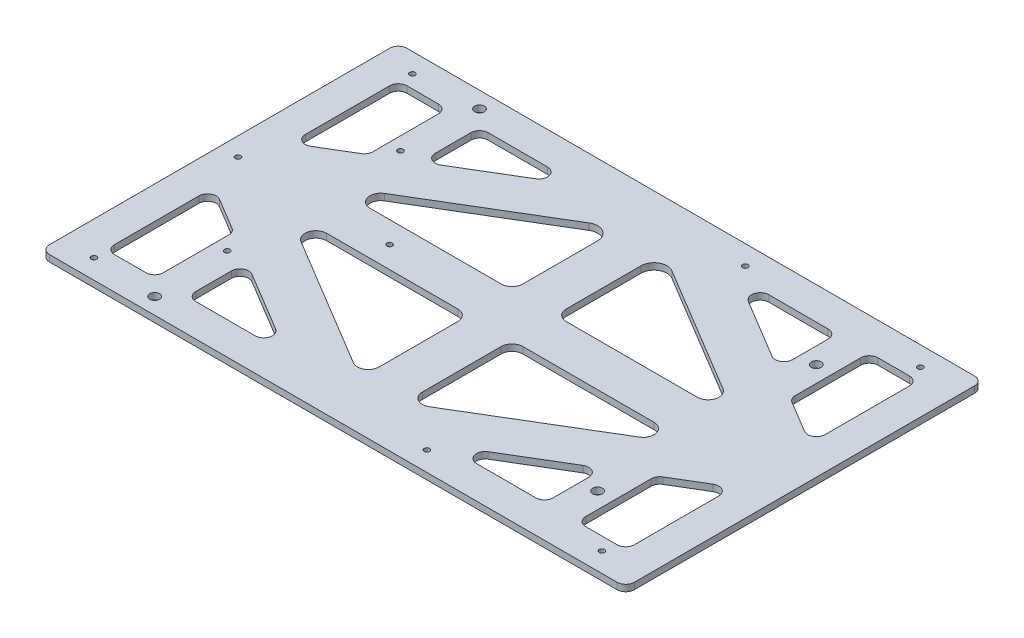
SolidWorks part; units mm, degrees
ref_plane "Alzado" through (0, 0, 0) normal (0, 0, 1) x (1, 0, 0)
ref_plane "Planta" through (0, 0, 0) normal (0, 1, 0) x (1, 0, 0)
ref_plane "Vista lateral" through (0, 0, 0) normal (1, 0, 0) x (0, 0, -1)
sketch "Croquis1" plane through (0, 0, 0) normal (0, 1, 0) x (1, 0, 0)
  line L1 (135, -82.5) -> (-135, -82.5)
  line L2 (135, -82.5) -> (135, 82.5)
  line L3 (135, 82.5) -> (-135, 82.5)
  line L4 (-135, -82.5) -> (-135, 82.5)
  line L5 (135, -82.5) -> (-135, 82.5) construction
  line L6 (135, 82.5) -> (-135, -82.5) construction
  point P0 (0, 0)
  dimension "D1" = 165
  dimension "D2" = 270
extrude "Saliente-Extruir1" add sketch "Croquis1" along normal blind 3
fillet "Redondeo1" radius 4 4 edges at (-135, 1.5, -82.5) (135, 1.5, -82.5) (135, 1.5, 82.5) (-135, 1.5, 82.5)
sketch "Croquis2" plane through (0, 3, 0) normal (0, 1, 0) x (1, 0, 0)
  line L0 (131, 82.5) -> (-131, 82.5) construction
  line L1 (135, -78.5) -> (135, 78.5) construction
  circle A0 centre (90, 50.5) radius 2.25
  dimension "D1" = 4.5
  dimension "D2" = 32
  dimension "D3" = 45
extrude "Cortar-Extruir1" cut sketch "Croquis2" against normal through all
mirror "Simetría1" about plane through (0, 0, 0) normal (0, 0, 1) of "Cortar-Extruir1"
sketch "Croquis3" plane through (0, 3, 0) normal (0, 1, 0) x (1, 0, 0)
  line L0 (-135, 78.5) -> (-135, -78.5) construction
  line L1 (131, 82.5) -> (-131, 82.5) construction
  line L2 (-135, 0) -> (-113.8944, 0) construction
  circle A0 centre (-90, 75) radius 2.25
  circle A1 centre (-90, -75) radius 2.25
  dimension "D1" = 4.5
  dimension "D2" = 45
  dimension "D3" = 7.5
extrude "Cortar-Extruir2" cut sketch "Croquis3" against normal through all
sketch "Croquis4" plane through (0, 3, 0) normal (0, 1, 0) x (1, 0, 0)
  line L0 (0, 82.5) -> (0, -82.5) construction
  line L1 (131, 82.5) -> (-131, 82.5) construction
  line L2 (-131, -82.5) -> (131, -82.5) construction
  line L3 (-135, 0) -> (135, 0) construction
  line L4 (-135, 78.5) -> (-135, -78.5) construction
  line L5 (135, -78.5) -> (135, 78.5) construction
  line L6 (0, -82.5) -> (131, -82.5) construction
  line L7 (135, -82.5) -> (135, 78.5) construction
  line L8 (131, 82.5) -> (0, 82.5) construction
  line L9 (116, 67.5) -> (101.5, 67.5)
  line L12 (110.2817, 0) -> (2.6409, -64.5845) construction
  line L13 (131, 67.5) -> (-131, 67.5) construction
  line L14 (4.9275, 63.2125) -> (110.2817, 0) construction
  line L15 (15, 10) -> (75.5635, 10)
  line L16 (131, 82.5) -> (-131, 82.5) construction
  line L17 (15, -10) -> (75.5635, -10)
  line L18 (10, 49.5719) -> (10, 15)
  line L19 (19.087, 54.7169) -> (78.136, 19.2875)
  line L20 (78.136, -19.2875) -> (17.5725, -55.6256)
  line L24 (49.038, 60.07) -> (76.442, 43.6276)
  line L29 (15.2174, 80.3624) -> (149.1548, 0) construction
  line L30 (90, 50.5) -> (90, 67.5) construction
  line L31 (149.1548, 0) -> (12.9308, -81.7344) construction
  line L32 (99.442, 29.8276) -> (113.942, 21.1276)
  line L34 (82.5, 63.5) -> (82.5, 47.0576)
  line L36 (97.5, 63.5) -> (97.5, 33.2576)
  line L37 (120, 24.5576) -> (120, 63.5)
  line L38 (78.5, 67.5) -> (51.096, 67.5)
  line L39 (10, -15) -> (10, -51.3381)
  arc A0 (78.5, 67.5) -> (82.5, 63.5) centre (78.5, 63.5) cw
  arc A1 (82.5, 47.0576) -> (76.442, 43.6276) centre (78.5, 47.0576) cw
  arc A2 (49.038, 60.07) -> (51.096, 67.5) centre (51.096, 63.5) cw
  arc A3 (120, 63.5) -> (116, 67.5) centre (116, 63.5) ccw
  arc A4 (120, 24.5576) -> (113.942, 21.1276) centre (116, 24.5576) cw
  arc A5 (99.442, 29.8276) -> (97.5, 33.2576) centre (101.5, 33.2576) cw
  arc A6 (101.5, 67.5) -> (97.5, 63.5) centre (101.5, 63.5) ccw
  arc A7 (10, -51.3381) -> (17.5725, -55.6256) centre (15, -51.3381) ccw
  arc A9 (10, 49.5719) -> (19.087, 54.7169) centre (16, 49.5719) cw
  arc A10 (75.5635, 10) -> (78.136, 19.2875) centre (75.5635, 15) ccw
  arc A11 (75.5635, -10) -> (78.136, -19.2875) centre (75.5635, -15) cw
  arc A12 (15, 10) -> (10, 15) centre (15, 15) cw
  arc A13 (15, -10) -> (10, -15) centre (15, -15) ccw
  point P44 (97.5, 30.9929)
  point P64 (10, -10)
  dimension "D5" = 4
  dimension "D6" = 4
  dimension "D7" = 5
  dimension "D13" = 5
  dimension "D14" = 5
  dimension "D2" = 22.43
  dimension "D4" = 15
  dimension "D8" = 15
  dimension "D9" = 38.8724
  dimension "D10" = 10
  dimension "D11" = 10
  dimension "D12" = 10
  dimension "D1" = 15
  dimension "D3" = 20
extrude "Cortar-Extruir3" cut sketch "Croquis4" against normal through all
mirror "Simetría2" about plane through (0, 0, 0) normal (0, 0, 1) of face at (117.4709, 1.5, -21.9597) of face at (106.692, 1.5, -25.4776) of face at (98.2451, 1.5, -31.4147) of face at (97.5, 1.5, -48.3788) of face at (99.0858, 1.5, -65.9142) of face at (108.75, 1.5, -67.5) of face at (118.4142, 1.5, -65.9142) of face at (120, 1.5, -44.0288) of face at (80.9142, 1.5, -65.9142) of face at (82.5, 1.5, -55.2788) of face at (79.9709, 1.5, -44.4597) of face at (62.74, 1.5, -51.8488) of face at (48.6541, 1.5, -64.1764) of face at (64.798, 1.5, -67.5)
mirror "Simetría4" about plane through (0, 0, 0) normal (1, 0, 0) of "Cortar-Extruir3"
mirror "Simetría6" about plane through (0, 0, 0) normal (0, 0, 1) of face at (-64.798, 1.5, -67.5) of face at (-48.6541, 1.5, -64.1764) of face at (-62.74, 1.5, -51.8488) of face at (-79.9709, 1.5, -44.4597) of face at (-80.9142, 1.5, -65.9142) of face at (-82.5, 1.5, -55.2788) of face at (-97.5, 1.5, -48.3788) of face at (-98.2451, 1.5, -31.4147) of face at (-106.692, 1.5, -25.4776) of face at (-117.4709, 1.5, -21.9597) of face at (-120, 1.5, -44.0288) of face at (-99.0858, 1.5, -65.9142) of face at (-118.4142, 1.5, -65.9142) of face at (-108.75, 1.5, -67.5)
sketch "Croquis5" plane through (0, 3, 0) normal (0, 1, 0) x (1, 0, 0)
  line L0 (135, -78.5) -> (135, 78.5) construction
  line L1 (-131, -82.5) -> (131, -82.5) construction
  line L2 (131, 82.5) -> (-131, 82.5) construction
  circle A0 centre (-119.5, 73.5) radius 1.75
  circle A1 centre (34.2, 73.5) radius 1.75
  circle A2 centre (115, 73.5) radius 1.75
  circle A3 centre (115, -73.5) radius 1.75
  circle A4 centre (34.2, -73.5) radius 1.75
  circle A5 centre (-119.5, -73.5) radius 1.75
  point P0 (-119.5, 73.5)
  point P3 (34.2, 73.5)
  point P6 (115, 73.5)
  point P9 (115, -73.5)
  point P12 (34.2, -73.5)
  point P15 (-119.5, -73.5)
  dimension "D1" = 20
  dimension "D2" = 80.8
  dimension "D3" = 153.7
  dimension "D4" = 9
  dimension "D5" = 9
hole_wizard "Taladro roscado M31" positions "Croquis5" profile "Croquis6" tap size "M3" standard "ISO"
sketch "Croquis6" plane through (-119.5, 3, -73.5) normal (1, 0, 0) x (0, 0, 1)
  line L0 (0, 0) -> (0, 9.2511)
  line L1 (0, 9.2511) -> (1.25, 8.5)
  line L2 (1.25, 8.5) -> (1.25, 0)
  line L5 (1.25, 0) -> (0, 0)
  line L10 (0, 9.2511) -> (-1.25, 8.5) construction
  line L11 (0, -6.35) -> (0, 107.95) construction
  dimension "Diámetro de perforador para roscar" = 2.5
  dimension "Profundidad de perforador para roscar" = 8.5
  dimension "Ángulo de perforador" = 118
cosmetic thread "Rosca de taladro1" parameters "D1"=6, "D2"=3
cosmetic thread "Rosca de taladro2" parameters "D1"=6, "D2"=3
cosmetic thread "Rosca de taladro3" parameters "D1"=6, "D2"=3
cosmetic thread "Rosca de taladro4" parameters "D1"=6, "D2"=3
cosmetic thread "Rosca de taladro5" parameters "D1"=6, "D2"=3
cosmetic thread "Rosca de taladro6" parameters "D1"=6, "D2"=3
sketch "Croquis9" plane through (0, 3, 0) normal (0, 1, 0) x (1, 0, 0)
  point P0 (-126.5, 0)
  point P1 (-91.5, -40)
  point P3 (-56.5, 0)
  point P5 (-91.5, 40)
hole_wizard "Taladro roscado M32" positions "Croquis9" profile "Croquis10" tap size "M3" standard "ISO"
sketch "Croquis10" plane through (-126.5, 3, 0) normal (1, 0, 0) x (0, 0, 1)
  line L0 (0, 0) -> (0, 9.2511)
  line L1 (0, 9.2511) -> (1.25, 8.5)
  line L2 (1.25, 8.5) -> (1.25, 0)
  line L5 (1.25, 0) -> (0, 0)
  line L10 (0, 9.2511) -> (-1.25, 8.5) construction
  line L11 (0, -6.35) -> (0, 107.95) construction
  dimension "Diámetro de perforador para roscar" = 2.5
  dimension "Profundidad de perforador para roscar" = 8.5
  dimension "Ángulo de perforador" = 118
cosmetic thread "Rosca de taladro7" parameters "D1"=6, "D2"=3
cosmetic thread "Rosca de taladro8" parameters "D1"=6, "D2"=3
cosmetic thread "Rosca de taladro9" parameters "D1"=6, "D2"=3
cosmetic thread "Rosca de taladro10" parameters "D1"=6, "D2"=3
